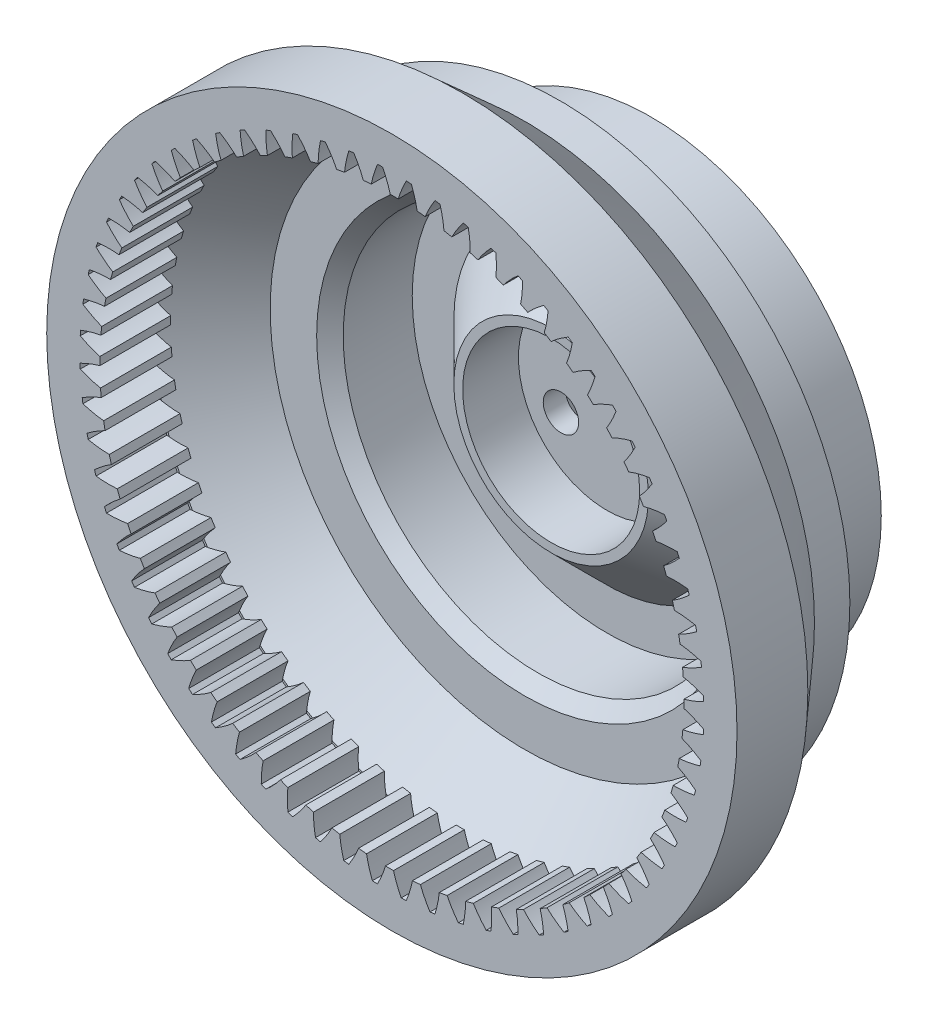
SolidWorks part; units mm, degrees
ref_plane "Front Plane" through (0, 0, 0) normal (0, 0, 1) x (1, 0, 0)
ref_plane "Top Plane" through (0, 0, 0) normal (0, 1, 0) x (1, 0, 0)
ref_plane "Right Plane" through (0, 0, 0) normal (1, 0, 0) x (0, 0, -1)
sketch "Sketch1" plane through (0, 0, 0) normal (0, 0, 1) x (1, 0, 0)
  circle A0 centre (0, 0) radius 35.25 construction
  circle A1 centre (0, 0) radius 39
  circle A2 centre (0, 0) radius 33
  dimension "D1" = 70.5
  dimension "D2" = 66
  dimension "D3" = 78
extrude "Boss-Extrude1" add sketch "Sketch1" along normal mid plane 8 contours A1 A0 region at (-37.8969, 0, 0)
sketch "Sketch3" plane through (0, 0, 0) normal (0, 0, 1) x (1, 0, 0)
  line L0 (0, 0) -> (31.9495, 0) construction
  line L1 (0, 0) -> (35.2245, -1.3393) construction
  line L3 (0, 0) -> (31.8573, 2.4261) construction
  circle A0 centre (0, 0) radius 31.9495 construction
  circle A1 centre (0, 0) radius 35.25
  circle A3 centre (0, 0) radius 34 construction
  circle A5 centre (0, 0) radius 33
  spline S0 degree 4 poles (31.9495, 0) (31.9605, 0.0002) (31.9911, 0.0011) (32.049, 0.0048) (32.1432, 0.0135) (32.2631, 0.0286) (32.4178, 0.0527) (32.5993, 0.087) (32.7982, 0.1309) (33.0136, 0.1853) (33.2277, 0.2453) (33.4403, 0.3107) (33.6513, 0.3807) (33.9057, 0.4711) (34.2092, 0.5876) (34.5613, 0.7353) (34.9574, 0.9163) (35.3572, 1.1152) (35.7474, 1.3226) (36.1376, 1.5456) (36.5123, 1.7708) (36.8969, 2.0183) (37.2496, 2.2536) (37.6394, 2.5321) (37.9525, 2.7611) (38.3593, 3.0788) (38.5978, 3.2711) (38.8746, 3.5014) (38.9964, 3.6064) (39.0715, 3.6711) knots 0 0 0 0 0 0.005377 0.015084 0.028532 0.04661 0.064855 0.092111 0.119476 0.146842 0.174209 0.201575 0.228941 0.256307 0.307035 0.361767 0.4165 0.471232 0.525964 0.580697 0.635429 0.690161 0.744894 0.799626 0.854358 0.909091 0.954545 1 1 1 1 1 construction
  spline S1 degree 4 poles (31.9495, 0) (31.9605, 0.0002) (31.9911, 0.0011) (32.049, 0.0048) (32.1432, 0.0135) (32.2631, 0.0286) (32.4178, 0.0527) (32.5993, 0.087) (32.7982, 0.1309) (33.0136, 0.1853) (33.2277, 0.2453) (33.4403, 0.3107) (33.6513, 0.3807) (33.9057, 0.4711) (34.2092, 0.5876) (34.5613, 0.7353) (34.9574, 0.9163) (35.3572, 1.1152) (35.7474, 1.3226) (36.1376, 1.5456) (36.5123, 1.7708) (36.8969, 2.0183) (37.2496, 2.2536) (37.6394, 2.5321) (37.9525, 2.7611) (38.2711, 3.0099) (38.4255, 3.1328) (38.5041, 3.1963) knots 0 0 0 0 0 0.005377 0.015084 0.028532 0.04661 0.064855 0.092111 0.119476 0.146842 0.174209 0.201575 0.228941 0.256307 0.307035 0.361767 0.4165 0.471232 0.525964 0.580697 0.635429 0.690161 0.744894 0.799626 0.854358 0.909091 0.909091 0.909091 0.909091 0.909091
  spline S2 degree 4 poles (31.8573, 2.4261) (31.8682, 2.4268) (31.8988, 2.4282) (31.9568, 2.4289) (32.0515, 2.4274) (32.1722, 2.4214) (32.3282, 2.4091) (32.5118, 2.3886) (32.7134, 2.36) (32.9324, 2.3222) (33.1504, 2.2785) (33.3674, 2.2295) (33.583, 2.1758) (33.8436, 2.1049) (34.155, 2.0118) (34.5173, 1.8913) (34.926, 1.7409) (35.3398, 1.5729) (35.7447, 1.3957) (36.1507, 1.203) (36.5413, 1.0069) (36.9436, 0.7893) (37.3132, 0.5815) (37.723, 0.3334) (38.0525, 0.1288) (38.4823, -0.1571) (38.7347, -0.3307) (39.0283, -0.5393) (39.1577, -0.6348) (39.2374, -0.6936) knots 0 0 0 0 0 0.005377 0.015084 0.028532 0.04661 0.064855 0.092111 0.119476 0.146842 0.174209 0.201575 0.228941 0.256307 0.307035 0.361767 0.4165 0.471232 0.525964 0.580697 0.635429 0.690161 0.744894 0.799626 0.854358 0.909091 0.954545 1 1 1 1 1 construction
  spline S3 degree 4 poles (31.8573, 2.4261) (31.8682, 2.4268) (31.8988, 2.4282) (31.9568, 2.4289) (32.0515, 2.4274) (32.1722, 2.4214) (32.3282, 2.4091) (32.5118, 2.3886) (32.7134, 2.36) (32.9324, 2.3222) (33.1504, 2.2785) (33.3674, 2.2295) (33.583, 2.1758) (33.8436, 2.1049) (34.155, 2.0118) (34.5173, 1.8913) (34.926, 1.7409) (35.3398, 1.5729) (35.7447, 1.3957) (36.1507, 1.203) (36.5413, 1.0069) (36.9436, 0.7893) (37.3132, 0.5815) (37.723, 0.3334) (38.0525, 0.1288) (38.3892, -0.0951) (38.5524, -0.2059) (38.6356, -0.2633) knots 0 0 0 0 0 0.005377 0.015084 0.028532 0.04661 0.064855 0.092111 0.119476 0.146842 0.174209 0.201575 0.228941 0.256307 0.307035 0.361767 0.4165 0.471232 0.525964 0.580697 0.635429 0.690161 0.744894 0.799626 0.854358 0.909091 0.909091 0.909091 0.909091 0.909091
  dimension "D1" = 63.8991
  dimension "D2" = 70.5
  dimension "D3" = 68
  dimension "D5" = 66
  dimension "D4" = 2.177
extrude "Cut-Extrude1" cut sketch "Sketch3" against normal through all both and the other way through all contours A5 A1 S3 region at (33.8915, 1.2886, 0)
pattern_circular "CirPattern7" count 68 over 360 about axis through (0, 0, 4) along (0, 0, -1) of "Cut-Extrude1"
sketch "Sketch4" plane through (0, 0, 0) normal (0, 1, 0) x (1, 0, 0)
  line L0 (0, 0) -> (0, 34.2574) construction
  line L21 (-26, 25.3) -> (-22, 25.3)
  line L22 (-22, 25.3) -> (-22, 15)
  line L23 (-26, 25.3) -> (-26, 15)
  line L28 (-26, 15) -> (-22, 15) construction
  line L30 (-35, 4) -> (-39, 4)
  line L31 (39, 4) -> (-39, 4) construction
  line L32 (-35, 4) -> (-28.75, 11)
  line L33 (-39, 4) -> (-32.75, 11)
  line L34 (-32.75, 11) -> (-28.75, 11)
  line L35 (-32.75, 11) -> (-32.75, 15)
  line L36 (-32.75, 15) -> (-26, 15)
  line L37 (-22, 15) -> (-22, 11)
  line L38 (-22, 11) -> (-28.75, 11)
  line L39 (-28.75, 11) -> (-22, 11)
  dimension "D1" = 4
  dimension "D2" = 26
  dimension "D3" = 4
  dimension "D5" = 10.3
  dimension "D4" = 7
  dimension "D6" = 28.75
  dimension "D7" = 4
  dimension "D8" = 4
revolve "Revolve1" add sketch "Sketch4" angle 360 about L0 region at (-25.7236, 0, -16.4986) region at (-33.875, 0, -7.5)
sketch "Sketch5" plane through (0, 0, -25.3) normal (0, 0, -1) x (-1, 0, 0)
  circle A1 centre (0, 0) radius 6 construction
  circle A3 centre (0, 0) radius 22 construction
  circle A4 centre (0, 0) radius 22
  dimension "D1" = 12
extrude "Boss-Extrude2" add sketch "Sketch5" against normal blind 5
sketch "Sketch10" plane through (0, 0, -15) normal (0, 0, -1) x (-1, 0, 0)
  circle A1 centre (0, 0) radius 26 construction
  circle A2 centre (0, 0) radius 27.5
  circle A3 centre (0, 0) radius 27.5
  circle A4 centre (0, 0) radius 26
  dimension "D1" = 1.5
extrude "Boss-Extrude7" add sketch "Sketch10" along normal blind 1
sketch "Sketch11" plane through (0, 0, -25.3) normal (0, 0, -1) x (-1, 0, 0)
  circle A0 centre (0, 0) radius 6 construction
  circle A1 centre (0, 6) radius 2
  circle A2 centre (5.1962, -3) radius 2
  circle A3 centre (-5.1962, -3) radius 2
  point P14 (0, 0)
  dimension "D1" = 12
  dimension "D2" = 4
extrude "Cut-Extrude2" cut sketch "Sketch11" against normal up to next
sketch "Sketch12" plane through (0, 0, 0) normal (-1, 0, 0) x (0, 1, 0)
  line L1 (8, 25.3) -> (4, 25.3)
  line L2 (6, 25.3) -> (6, 20.6833) construction
  line L3 (6, 25.3) -> (1.5, 25.3)
  line L4 (1.5, 25.3) -> (4, 22.8)
  line L5 (4, 22.8) -> (4, 25.3)
  line L6 (8, 25.3) -> (4, 25.3) construction
  line L7 (8, 25.3) -> (4, 25.3)
  dimension "D1" = 2.5
  dimension "D2" = 4.5
revolve "Cut-Revolve1" cut sketch "Sketch12" angle 360 about L2 region at (0, 3.1667, -24.4667)
pattern_circular "CirPattern8" count 3 over 360 about axis through (0, 0, 0) along (0, 0, 1) of "Cut-Revolve1"
sketch "Sketch13" plane through (0, 0, -20.3) normal (0, 0, 1) x (1, 0, 0)
  circle A0 centre (0, 0) radius 10
  circle A1 centre (0, 0) radius 11
  dimension "D1" = 20
extrude "Boss-Extrude8" add sketch "Sketch13" along normal blind 6.3
chamfer "Chamfer1" distance 6.3 angle 45 1 edges at (-11, 0, -20.3)
chamfer "Chamfer2" distance 1.5 angle 45 1 edges at (22, 0, -11)
equation "\"Nr_s\"= \"Ns\" + \"Np_b\" + \"Np_s\"'num teeth"
equation "\"module\"= 1"
equation "\"pressure_angle\"= 20deg"
equation "\"h_a\"= 1 * \"module\"'addendum"
equation "\"h_f\"= 1.25 * \"module\"'dedendum"
equation "\"clr_tip_root\"= \"h_f\" - \"h_a\"'clearance of gear tooth tip and root"
equation "\"dp_r_s\"= \"module\" * \"Nr_s\"'PCD"
equation "\"db_r_s\"= \"dp_r_s\" * cos ( \"pressure_angle\" )'base CD"
equation "\"D1@Sketch1\"= \"dp_r_s\" + 2 * \"h_f\"'dedendum circle"
equation "\"fw_r_s\"= 8mm'face width"
equation "\"D1@Boss-Extrude1\"=\"fw_r_s\""
equation "\"alpha_r_s\"= sqr ( \"dp_r_s\" ^ 2 - \"db_r_s\" ^ 2 ) / \"db_r_s\" * 180 / pi - \"pressure_angle\""
equation "\"beta_r_s\"= ( 360 / ( 4 * \"Nr_s\" ) + \"alpha_r_s\" ) * 2"
equation "\"D2@Sketch1\"=\"Nr_s\"*\"module\"-2*\"h_a\""
equation "\"D1@Sketch3\"= \"db_r_s\""
equation "\"D2@Sketch3\"= \"dp_r_s\" + 2*\"h_f\""
equation "\"D3@Sketch3\"=\"dp_r_s\""
equation "\"D4@Sketch3\"= \"beta_r_s\" / 2"
equation "\"D5@Sketch3\"= \"dp_r_s\" - 2 * \"h_a\"'addendum"
equation "\"D1@CirPattern7\"=\"Nr_s\""
equation "\"bearing_ID\"= \"module\" * ( \"Ns\" + \"Np_b\") + 6"
equation "\"bearing_OD\"= 1.18 * \"bearing_ID\" + 8.57"
equation "\"bearing_height\"= 0.09 * \"bearing_ID\" + 4.62"
equation "\"clearance_planet\"=1.5"
equation "\"case_dist\"= \"sec_carrier_thickness\" + \"clearance_planet\" + \"sun_coupler_hub_thickness\" - \"case_mounting_surface_height\""
equation "\"Motor_case_OD_max\"= \"case_mounting_PCD\" + \"case_mounting_hole_allen_socket_dia\" + \"clearance_case_mount_holes_shell_thickness\" * 2"
equation "\"case_mounting_PCD\"= \"motor_case_OD_base\" + \"case_mounting_hole_shift\" * 2"
equation "\"bearing mount thickness\"= IIF((\"bearing_OD\" + \"output_mounting_hole_dia\" * 4) > (\"Nr_s\" * \"module\" + 2 * \"h_b\"), \"output_mounting_hole_dia\" * 2, ((\"Nr_s\" * \"module\" + 2 * \"h_b\" - (\"bearing_OD\" + \"output_mounting_hole_dia\" * 4)) / 2) + \"output_mounting_hole_dia\" * 2 + \"standard_clearance_1_5mm\")"
equation "\"D3@Sketch1\"=\"ring_OD\""
equation "\"case_mounting_hole_dia\"=3"
equation "\"output_mounting_PCD\"= \"bearing_OD\" + \"bearing mount thickness\""
equation "\"output_mounting_hole_dia\"= 4"
equation "\"clearance_case_mount_holes_shell_thickness\"= 1"
equation "\"motor_case_OD_base\"= \"motor_OD\" + \"clearance_motor_and_case\" * 2 + \"Motor_case_thickness\" * 2"
equation "\"sec_carrier_thickness\"= 5"
equation "\"sun_coupler_hub_thickness\"= 4"
equation "\"clearance_sun_coupler_sec_carrier\"= 1.5"
equation "\"clearance_motor_and_case\"= IIF( ((\"Ns\" + \"Np_b\" * 2) * \"module\") < \"motor_OD\", 5, (((\"Ns\" + \"Np_b\" * 2) * \"module\" - \"motor_OD\") * 0.5 + 5) )"
equation "\"motor_OD\"= 72"
equation "\"Motor_case_thickness\"= 2.5"
equation "\"Motor_case_ID\"= \"motor_OD\" + \"clearance_motor_and_case\" * 2"
equation "\"case_mounting_hole_shift\"= \"case_mounting_hole_dia\" / 2 - 0.5"
equation "\"output_mounting_nut_wrench_size\"= 7"
equation "\"output_mounting_nut_thickness\"= 3.2"
equation "\"case_mounting_hole_allen_socket_dia\"= 5.5"
equation "\"output_mounting_nut_depth\"= 3"
equation "\"case_mounting_bolt_depth\"= 4.5"
equation "\"Ns\"= 20"
equation "\"ring_radial_thickness\"= 5"
equation "\"ring_OD\"= \"Nr_s\" * \"module\" + \"ring_radial_thickness\" * 2"
equation "\"ring_to_chamfer_clearance\"= \"clearance_planet\""
equation "\"Motor_case_OD_base_to_chamfer\"=5"
equation "\"pattern_offset_from_motor_case_OD_base\"= 3"
equation "\"pattern_bulge_dia\"= 3"
equation "\"pattern_num_bulge\"= 18"
equation "\"pattern_depth\"= 2"
equation "\"motor_height\"= 27"
equation "\"case_mounting_wrench_size\"= 5.5"
equation "\"case_mounting_nut_clearance\"= 2"
equation "\"base_plate_thickness\"= 4"
equation "\"case_mounting_nut_thickness\"= 2.4"
equation "\"case_mounting_surface_height\"= 4"
equation "\"motor_mount_hole_PCD\"= 32"
equation "\"motor_mount_hole_dia\"= 4"
equation "\"motor_mount_hole_num\"= 4"
equation "\"central_hole_offset_from_motor_mount_PCD\"= 5"
equation "\"wire_slot_dist_from_center\"= 33"
equation "\"wire_slot_length\"= 10"
equation "\"wire_slot_radius\"= 4"
equation "\"driver_upper_holes_dist_from_center\"= 23"
equation "\"driver_lower_holes_dist_from_center\"= 15"
equation "\"driver_side_holes_dist_from_center\"= 20"
equation "\"driver_mount_holes_dia\"= 2.5"
equation "\"driver_mount_inserts_OD\"= 3.5"
equation "\"driver_mount_thickness\"= 1.5"
equation "\"driver_mount_height\"= 4"
equation "\"air_flow_hole_offset\"= 3"
equation "\"pressure angle\"= 20deg"
equation "\"h_b\"= 1.25 * \"module\"'dedendum"
equation "\"fw_p_s\"= \"fw_r_s\" + \"clearance_planet\""
equation "\"num_planet\"= 4"
equation "\"planet_pin_bolt_dia\"= 5"
equation "\"planet_pin_socket_head_dia\"= 8.5"
equation "\"carrier_PCD\"= ( \"Np_b\" + \"Ns\" ) * \"module\""
equation "\"planet_shaft_dia\"= 8"
equation "\"planet_shaft_step_offset\"= 1"
equation "\"carrier_trapezoidal_support_sun_offset\"= 5"
equation "\"carrier_trapezoidal_support_hole_PCD_offset_bearing_ID\"= 4"
equation "\"carrier_trapezoidal_support_hole_dia\"= 3"
equation "\"carrier_trapezoidal_support_hole_socket_head_dia\"= 5.5"
equation "\"carrier_bearing_step_width\"= 1.5"
equation "\"standard_clearance_1_5mm\"=1.5"
equation "\"standard_fillet_1_5mm\"= 1.5"
equation "\"sun_shaft_bearing_OD\"= 12"
equation "\"sun_shaft_bearing_width\"= 3.5"
equation "\"standard_bearing_insertion_chamfer\"= 0.5"
equation "\"carrier_trapezoidal_support_hole_wrench_size\"= 5.5"
equation "\"planet_pin_bolt_wrench_size\"= 8"
equation "\"planet_bearing_OD\"= 12"
equation "\"planet_bearing_width\"= 3.5"
equation "\"planet_bore\"= 10"
equation "\"motor_output_hole_PCD\"= 22"
equation "\"motor_output_hole_dia\"= 3"
equation "\"motor_output_hole_num\"= 4"
equation "\"Np_b\"= 26"
equation "\"dp_s\"= \"module\" * \"Ns\"'PCD"
equation "\"db_s\"= \"dp_s\" * cos ( \"pressure angle\" )'base CD"
equation "\"fw_s_calc\"= 10mm'face width"
equation "\"alpha_s\"= sqr ( \"dp_s\" ^ 2 - \"db_s\" ^ 2 ) / \"db_s\" * 180 / pi - \"pressure angle\""
equation "\"beta_s\"= ( 360 / ( 4 * \"Ns\" ) - \"alpha_s\" ) * 2"
equation "\"dp_p_b\"= \"module\" * \"Np_b\"'PCD"
equation "\"db_p_b\"= \"dp_p_b\" * cos ( \"pressure angle\" )'base CD"
equation "\"alpha_p_b\"= sqr ( \"dp_p_b\" ^ 2 - \"db_p_b\" ^ 2 ) / \"db_p_b\" * 180 / pi - \"pressure angle\""
equation "\"beta_p_b\"= ( 360 / ( 4 * \"Np_b\" ) - \"alpha_p_b\" ) * 2"
equation "\"sun_shaft_bearing_ID\"= 8"
equation "\"sun_hub_dia\"= \"motor_output_hole_PCD\" + \"motor_output_hole_dia\" + \"standard_clearance_1_5mm\" * 2"
equation "\"sun_central_bolt_dia\"= 5"
equation "\"sun_central_bolt_socket_head_dia\"= 8.5"
equation "\"fw_s_used\"= \"fw_p_s\" + \"fw_p_b\" + \"clearance_planet\" + \"sec_carrier_thickness\" + \"standard_clearance_1_5mm\" - \"carrier_small_ring_inner_bearing_flap\" +  \"standard_clearance_1_5mm\" "
equation "\"motor_output_hole_CSK_OD\"= 9'8.96 is exact value"
equation "\"motor_output_hole_CSK_head_height\"= 2.5"
equation "\"bearing_retainer_thickness\"= 2"
equation "\"Np_s\"= 22"
equation "\"fw_p_b\"= 8"
equation "\"dp_p_s\"= \"module\" * \"Np_s\"'PCD"
equation "\"db_p_s\"= \"dp_p_s\" * cos ( \"pressure angle\" )'base CD"
equation "\"alpha_p_s\"= sqr ( \"dp_p_s\" ^ 2 - \"db_p_s\" ^ 2 ) / \"db_p_s\" * 180 / pi - \"pressure angle\""
equation "\"beta_p_s\"= ( 360 / ( 4 * \"Np_s\" ) - \"alpha_p_s\" ) * 2"
equation "\"Nr_b\"= \"Ns\" + \"Np_b\" * 2"
equation "\"dp_r_b\"= \"module\" * \"Nr_b\"'PCD"
equation "\"db_r_b\"= \"dp_r_b\" * cos ( \"pressure_angle\" )'base CD"
equation "\"fw_r_b\"= \"fw_p_b\"'face width"
equation "\"alpha_r_b\"= sqr ( \"dp_r_b\" ^ 2 - \"db_r_b\" ^ 2 ) / \"db_r_b\" * 180 / pi - \"pressure_angle\""
equation "\"beta_r_b\"= ( 360 / ( 4 * \"Nr_b\" ) + \"alpha_r_b\" ) * 2"
equation "\"ring_OD_b\"= \"Nr_b\" * \"module\" + \"ring_radial_thickness\" * 2"
equation "\"clr_tip_root_s\"= \"h_f\" - \"h_a\"'clearance of gear tooth tip and root"
equation "\"D2@Sketch4\"=\"bearing_ID\"/2"
equation "\"D5@Sketch4\"=\"bearing_height\" + 1"
equation "\"D4@Sketch4\"=\"carrier_thickness\" +\"clearance_planet\" + \"standard_clearance_1_5mm\""
equation "\"D6@Sketch4\"=(\"module\"*(\"Ns\"+\"Np_b\") + \"planet_pin_socket_head_dia\" + \"standard_clearance_1_5mm\"*2)*0.5"
equation "\"D1@Boss-Extrude8\"=\"bearing_height\" + \"carrier_thickness\" - \"carrier_small_ring_inner_bearing_height\""
equation "\"D1@Chamfer1\"=\"bearing_height\" + \"carrier_thickness\" - \"carrier_small_ring_inner_bearing_height\""
equation "\"D1@Chamfer2\"=\"standard_clearance_1_5mm\""
equation "\"small_ring_case_thickness\"= 4mm"
equation "\"D3@Sketch4\"=\"small_ring_case_thickness\""
equation "\"D7@Sketch4\"=\"small_ring_case_thickness\""
equation "\"D8@Sketch4\"=\"small_ring_case_thickness\""
equation "\"D1@Sketch4\"=\"small_ring_case_thickness\""
equation "\"carrier_thickness\"= 4mm"
equation "\"D1@Sketch10\"=\"standard_clearance_1_5mm\""
equation "\"D1@Boss-Extrude7\"=\"standard_clearance_1_5mm\"*2/3"
equation "\"D2@Sketch13\"=\"standard_clearance_1_5mm\"*2/3"
equation "\"small_ring_output_wall_thickness\"= 5mm"
equation "\"small_ring_output_wall_to_bearing_shaft_attachement_hole_dia\"= 4mm"
equation "\"small_ring_output_wall_to_bearing_shaft_attachement_hole_pcd\"= 12mm"
equation "\"small_ring_output_wall_to_bearing_shaft_attachement_hole_num\"= 3"
equation "\"small_ring_output_wall_to_bearing_shaft_attachement_hole_CSK_OD\"= 9mm"
equation "\"small_ring_output_wall_to_bearing_shaft_attachement_hole_CSK_head_height\"= 2.5mm"
equation "\"carrier_small_ring_inner_bearing_ID\"= 20mm"
equation "\"carrier_small_ring_inner_bearing_OD\"= 32mm"
equation "\"carrier_small_ring_inner_bearing_height\"= 7mm"
equation "\"D1@Sketch5\"=\"sun_shaft_bearing_OD\""
equation "\"D1@Boss-Extrude2\"=\"small_ring_output_wall_thickness\""
equation "\"D1@Sketch11\"=\"small_ring_output_wall_to_bearing_shaft_attachement_hole_pcd\""
equation "\"D2@Sketch11\"=\"small_ring_output_wall_to_bearing_shaft_attachement_hole_dia\""
equation "\"D3@Sketch11\"=\"small_ring_output_wall_to_bearing_shaft_attachement_hole_num\""
equation "\"D1@Sketch12\"=\"small_ring_output_wall_to_bearing_shaft_attachement_hole_CSK_head_height\""
equation "\"D2@Sketch12\"=\"small_ring_output_wall_to_bearing_shaft_attachement_hole_CSK_OD\"/2"
equation "\"D1@CirPattern8\"=\"small_ring_output_wall_to_bearing_shaft_attachement_hole_num\""
equation "\"D1@Sketch13\"=\"carrier_small_ring_inner_bearing_ID\""
equation "\"small_ring_output_wall_to_bearing_shaft_attachement_hole_depth\"= 6.5mm"
equation "\"small_ring_output_wall_to_bearing_shaft_attachement_nut_wrench\"= 7mm"
equation "\"small_ring_output_wall_to_bearing_shaft_attachement_nut_thickness\"= 3.2mm"
equation "\"carrier_small_ring_inner_bearing_flap\"= 2mm"
equation "\"gear_casing_big_ring_to_bearing_dist\"=\"fw_p_s\" + \"clearance_planet\" + \"carrier_thickness\" + \"standard_clearance_1_5mm\"*2/3 + \"small_ring_case_thickness\" "
equation "\"gear_casing_thickness\"= 4"
